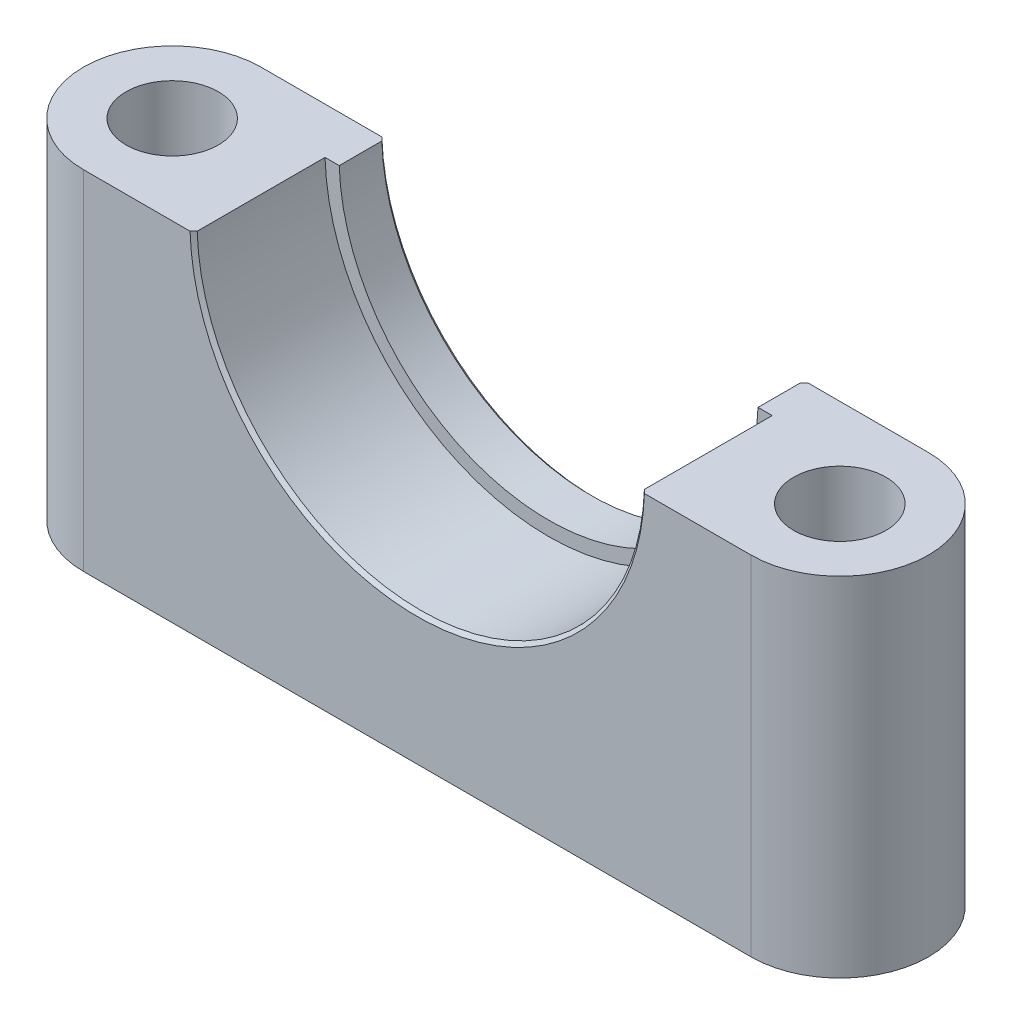
SolidWorks part; units mm, degrees
ref_plane "Front" through (0, 0, 0) normal (0, 0, 1) x (1, 0, 0)
ref_plane "Top" through (0, 0, 0) normal (0, 1, 0) x (1, 0, 0)
ref_plane "Right" through (0, 0, 0) normal (1, 0, 0) x (0, 0, -1)
sketch "Sketch1" plane through (0, 0, 0) normal (0, 1, 0) x (1, 0, 0)
  line L0 (-23.876, 0) -> (23.876, 0) construction
  line L1 (-23.876, 6.35) -> (23.876, 6.35)
  line L2 (-23.876, -6.35) -> (23.876, -6.35)
  arc A0 (-23.876, 6.35) -> (-23.876, -6.35) centre (-23.876, 0) ccw
  arc A1 (23.876, -6.35) -> (23.876, 6.35) centre (23.876, 0) ccw
  circle A2 centre (23.876, 0) radius 3.302
  circle A3 centre (-23.876, 0) radius 3.302
  point P3 (0, 0)
  dimension "D2" = 6.604
  dimension "D3" = 6.35
  dimension "D1" = 47.752
extrude "Boss-Extrude1" add sketch "Sketch1" along normal blind 24.892
sketch "Sketch2" plane through (0, 0, 6.35) normal (0, 0, 1) x (1, 0, 0)
  line L0 (-23.876, 0) -> (23.876, 0) construction
  line L1 (0, 25.4) -> (0, 0) construction
  circle A0 centre (0, 25.4) radius 16.002
  dimension "D1" = 32.004
  dimension "D2" = 25.4
extrude "Cut-Extrude1" cut sketch "Sketch2" against normal offset from surface (9.398 mm away) 3.302 up to face at (0, 12.446, -6.35)
sketch "Sketch3" plane through (0, 0, -3.048) normal (0, 0, 1) x (1, 0, 0)
  circle A0 centre (0, 25.4) radius 14.986
  arc A1 (-15.9939, 24.892) -> (15.9939, 24.892) centre (0, 25.4) ccw construction
  dimension "D1" = 29.972
extrude "Cut-Extrude2" cut sketch "Sketch3" against normal blind 17.78
chamfer "Chamfer1" distance 0.254 angle 45 2 edges at (0, 9.398, 6.35) (0, 10.414, -6.35)
